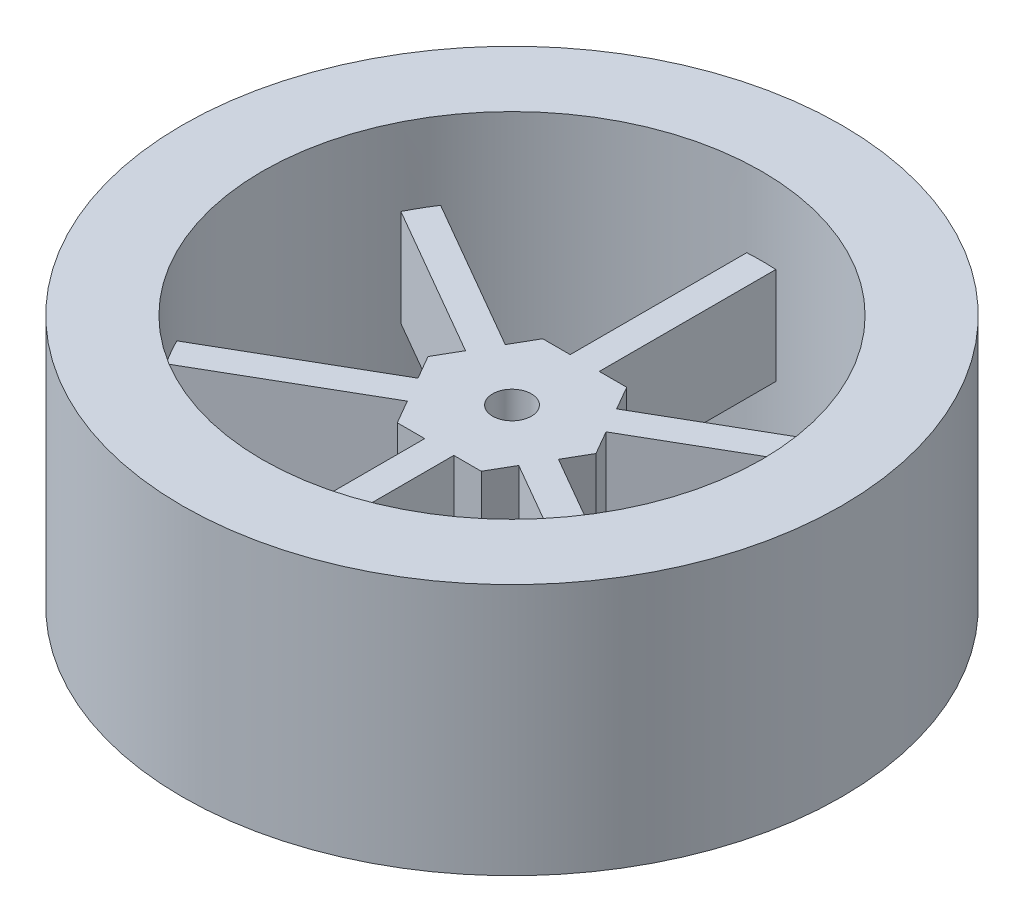
SolidWorks part; units mm, degrees
ref_plane "前视基准面" through (0, 0, 0) normal (0, 0, 1) x (1, 0, 0)
ref_plane "上视基准面" through (0, 0, 0) normal (0, 1, 0) x (1, 0, 0)
ref_plane "右视基准面" through (0, 0, 0) normal (1, 0, 0) x (0, 0, -1)
other "Configuration Table"
sketch "草图1" plane through (0, 0, 0) normal (0, 1, 0) x (1, 0, 0)
  circle A0 centre (0, 0) radius 34
  circle A1 centre (0, 0) radius 25.75
  dimension "D1" = 68
  dimension "D2" = 51.5
extrude "凸台-拉伸1" add sketch "草图1" along normal blind 26
ref_plane "基准面1" through (0, 13, 0) normal (0, 1, 0) x (1, 0, 0)
sketch "草图2" plane through (0, 13, 0) normal (0, 1, 0) x (1, 0, 0)
  line L0 (8.6603, 0) -> (4.3301, 7.5)
  line L1 (6.9282, 0) -> (3.4641, 6)
  line L2 (3.4641, 6) -> (-3.4641, 6)
  line L3 (-3.4641, 6) -> (-6.9282, 0)
  line L4 (-6.9282, 0) -> (-3.4641, -6)
  line L5 (-3.4641, -6) -> (3.4641, -6)
  line L6 (3.4641, -6) -> (6.9282, 0)
  line L7 (4.3301, 7.5) -> (-4.3301, 7.5)
  line L8 (-4.3301, 7.5) -> (-8.6603, 0)
  line L9 (-8.6603, 0) -> (-4.3301, -7.5)
  line L10 (-4.3301, -7.5) -> (4.3301, -7.5)
  line L11 (4.3301, -7.5) -> (8.6603, 0)
  line L12 (0, 0) -> (0, 25.75) construction
  line L13 (21.5123, 14.1522) -> (5.7452, 5.049)
  line L14 (-1.5, 25.7063) -> (1.5, 25.7063) construction
  line L15 (-1.5, 25.7063) -> (-1.5, 7.5)
  line L16 (-1.5, 7.5) -> (1.5, 7.5)
  line L17 (1.5, 25.7063) -> (1.5, 7.5)
  line L18 (-1.5, 25.7063) -> (1.5, 7.5) construction
  line L19 (-1.5, 7.5) -> (1.5, 25.7063) construction
  line L20 (23.0123, 11.5541) -> (7.2452, 2.451)
  line L21 (23.0123, -11.5541) -> (7.2452, -2.451)
  line L22 (21.5123, -14.1522) -> (5.7452, -5.049)
  line L23 (1.5, -25.7063) -> (1.5, -7.5)
  line L24 (-1.5, -25.7063) -> (-1.5, -7.5)
  line L25 (-21.5123, -14.1522) -> (-5.7452, -5.049)
  line L26 (-23.0123, -11.5541) -> (-7.2452, -2.451)
  line L27 (-23.0123, 11.5541) -> (-7.2452, 2.451)
  line L28 (-21.5123, 14.1522) -> (-5.7452, 5.049)
  line L29 (0, 0) -> (1.5, 7.5) construction
  line L30 (0, 0) -> (7.2452, 2.451) construction
  circle A0 centre (0, 0) radius 6 construction
  circle A1 centre (0, 0) radius 7.5 construction
  circle A2 centre (0, 0) radius 25.75 construction
  circle A3 centre (0, 0) radius 25.75
  circle A4 centre (0, 0) radius 2
  point P1 (0, 16.6031)
  dimension "D3" = 4
  dimension "D1" = 12
  dimension "D2" = 1.5
  dimension "D4" = 3
  dimension "D5" = 6
  dimension "D6" = 60
extrude "凸台-拉伸2" add sketch "草图2" along normal mid plane 10 contours L20 A3 L13 L0 | L22 A3 L21 L11 | L24 A3 L23 L10 | L26 A3 L25 L9 | L28 A3 L27 L8 | L17 A3 L15 L7 | L10 L11 L0 L7 L8 L9 L6 L5 L4 L3 L2 L1 region at (7.7543, 13, 1.1109) region at (14.3914, 13, -8.3089) region at (14.3914, 13, 8.3089) region at (0, 13, -16.6177) region at (0, 13, 16.6177) region at (-14.3914, 13, -8.3089) region at (-14.3914, 13, 8.3089)
extrude "凸台-拉伸3" add sketch "草图2<4>" along normal blind 5 contours L5 L6 L1 L2 L3 L4 region at (5.0374, 13, 2.9083)
sketch "草图2<4>" plane through (0, 13, 0) normal (0, 1, 0) x (1, 0, 0) same geometry as "草图2"
